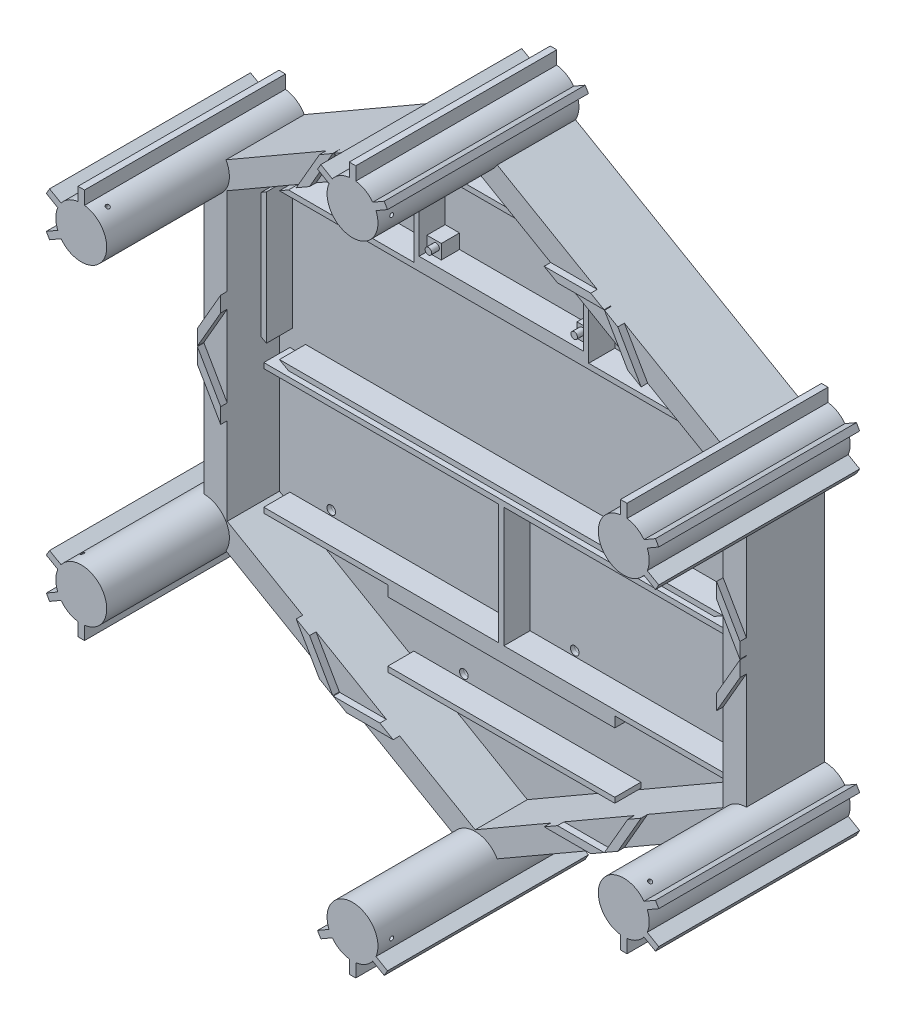
SolidWorks part; units mm, degrees
material "ABS"
ref_plane "Front Plane" through (0, 0, 0) normal (1, 0, 0) x (0, 1, 0)
ref_plane "Top Plane" through (0, 0, 0) normal (0, 0, 1) x (0, 1, 0)
ref_plane "Right Plane" through (0, 0, 0) normal (0, 1, 0) x (-1, 0, 0)
sketch "Sketch2" plane through (0, 0, 0) normal (0, 0, 1) x (0, 1, 0)
  line L0 (-1100, 0) -> (48900, 0) construction
  line L1 (120, 0) -> (60, 103.923)
  line L2 (60, 103.923) -> (-60, 103.923)
  line L3 (-60, 103.923) -> (-120, 0)
  line L4 (-120, 0) -> (-60, -103.923)
  line L5 (-60, -103.923) -> (60, -103.923)
  line L6 (60, -103.923) -> (120, 0)
  circle A0 centre (0, 0) radius 103.923 construction
  dimension "D1" = 120
extrude "Boss-Extrude1" add sketch "Sketch2" along normal mid plane 30
sketch "Sketch3" plane through (0, 0, 15) normal (0, 0, 1) x (1, 0, 0)
  line L0 (-95.0463, 65.125) -> (-76.4546, 75.8589) construction
  line L1 (-86.6025, 59.75) -> (-86.6025, 40.25) construction
  line L2 (-103.923, 60) -> (69.282, -40) construction
  line L3 (0, 0) -> (50000, 0) construction
  line L4 (0, 120) -> (-103.923, 60) construction
  line L5 (-111.6721, 54.0827) -> (-116.0719, 51.5425)
  line L6 (8.6603, 115) -> (43309.9304, -24885) construction
  line L7 (103.923, 50) -> (103.923, -49950) construction
  line L8 (95.2628, -65) -> (-43206.0074, -25065) construction
  line L9 (-8.6603, -115) -> (-43309.9304, 24885) construction
  line L10 (-86.6025, -50) -> (43214.6676, 24950) construction
  line L11 (0, -100) -> (0, 49900) construction
  line L14 (-117.3219, 66.2925) -> (-116.0719, 68.4575)
  line L16 (0, 0) -> (25000, 43301.2702) construction
  line L17 (0, 0) -> (25000, -43301.2702) construction
  line L18 (-114.0764, 61.9139) -> (-110.6886, 67.7817) construction
  line L19 (-112.9221, 63.7522) -> (-117.3219, 66.2925)
  line L20 (-111.6721, 65.9173) -> (-116.0719, 68.4575)
  line L21 (-112.9221, 56.2478) -> (-117.3219, 53.7075)
  line L23 (-105.173, 69.6695) -> (-105.173, 74.75)
  line L24 (-105.173, 74.75) -> (-102.673, 74.75)
  line L25 (-102.673, 69.6695) -> (-102.673, 74.75)
  line L26 (-117.3219, 53.7075) -> (-116.0719, 51.5425)
  line L27 (111.6721, -54.0827) -> (116.0719, -51.5425)
  line L28 (117.3219, -53.7075) -> (116.0719, -51.5425)
  line L29 (112.9221, -56.2478) -> (117.3219, -53.7075)
  line L30 (112.9221, -63.7522) -> (117.3219, -66.2925)
  line L31 (116.0719, -68.4575) -> (117.3219, -66.2925)
  line L32 (111.6721, -65.9173) -> (116.0719, -68.4575)
  line L33 (105.173, -69.6695) -> (105.173, -74.75)
  line L34 (105.173, -74.75) -> (102.673, -74.75)
  line L35 (102.673, -69.6695) -> (102.673, -74.75)
  line L36 (-8.9991, 123.7522) -> (-13.3989, 126.2925)
  line L37 (-12.1489, 128.4575) -> (-13.3989, 126.2925)
  line L38 (-7.7491, 125.9173) -> (-12.1489, 128.4575)
  line L39 (12.1489, 128.4575) -> (13.3989, 126.2925)
  line L40 (-1.25, 129.6695) -> (-1.25, 134.75)
  line L41 (1.25, 134.75) -> (-1.25, 134.75)
  line L42 (1.25, 129.6695) -> (1.25, 134.75)
  line L43 (7.7491, 125.9173) -> (12.1489, 128.4575)
  line L44 (8.9991, 123.7522) -> (13.3989, 126.2925)
  line L45 (-117.3219, -53.7075) -> (-116.0719, -51.5425)
  line L46 (-102.673, -69.6695) -> (-102.673, -74.75)
  line L47 (-105.173, -74.75) -> (-102.673, -74.75)
  line L48 (-105.173, -69.6695) -> (-105.173, -74.75)
  line L49 (-112.9221, -56.2478) -> (-117.3219, -53.7075)
  line L50 (-111.6721, -65.9173) -> (-116.0719, -68.4575)
  line L51 (-112.9221, -63.7522) -> (-117.3219, -66.2925)
  line L52 (-117.3219, -66.2925) -> (-116.0719, -68.4575)
  line L53 (-111.6721, -54.0827) -> (-116.0719, -51.5425)
  line L54 (102.673, 69.6695) -> (102.673, 74.75)
  line L55 (116.0719, 68.4575) -> (117.3219, 66.2925)
  line L56 (111.6721, 65.9173) -> (116.0719, 68.4575)
  line L57 (112.9221, 63.7522) -> (117.3219, 66.2925)
  line L58 (105.173, 69.6695) -> (105.173, 74.75)
  line L59 (112.9221, 56.2478) -> (117.3219, 53.7075)
  line L60 (117.3219, 53.7075) -> (116.0719, 51.5425)
  line L61 (111.6721, 54.0827) -> (116.0719, 51.5425)
  line L62 (105.173, 74.75) -> (102.673, 74.75)
  line L63 (8.9991, -123.7522) -> (13.3989, -126.2925)
  line L64 (7.7491, -125.9173) -> (12.1489, -128.4575)
  line L65 (1.25, -129.6695) -> (1.25, -134.75)
  line L66 (1.25, -134.75) -> (-1.25, -134.75)
  line L67 (-1.25, -129.6695) -> (-1.25, -134.75)
  line L68 (12.1489, -128.4575) -> (13.3989, -126.2925)
  line L69 (-7.7491, -125.9173) -> (-12.1489, -128.4575)
  line L70 (-12.1489, -128.4575) -> (-13.3989, -126.2925)
  line L71 (-8.9991, -123.7522) -> (-13.3989, -126.2925)
  arc A0 (-1.25, 129.6695) -> (-7.7491, 125.9173) centre (0, 120) ccw
  arc A1 (112.9221, 56.2478) -> (112.9221, 63.7522) centre (103.923, 60) ccw
  arc A2 (105.173, -69.6695) -> (111.6721, -65.9173) centre (103.923, -60) ccw
  arc A3 (-7.7491, -125.9173) -> (-1.25, -129.6695) centre (0, -120) ccw
  arc A4 (-112.9221, -56.2478) -> (-112.9221, -63.7522) centre (-103.923, -60) ccw
  arc A5 (-112.9221, 63.7522) -> (-112.9221, 56.2478) centre (-103.923, 60) ccw
  arc A6 (-105.173, 69.6695) -> (-111.6721, 65.9173) centre (-103.923, 60) ccw
  arc A7 (-111.6721, 54.0827) -> (-102.673, 69.6695) centre (-103.923, 60) ccw
  arc A8 (-111.6721, -65.9173) -> (-105.173, -69.6695) centre (-103.923, -60) ccw
  arc A9 (-102.673, -69.6695) -> (-111.6721, -54.0827) centre (-103.923, -60) ccw
  arc A10 (1.25, -129.6695) -> (7.7491, -125.9173) centre (0, -120) ccw
  arc A11 (8.9991, -123.7522) -> (-8.9991, -123.7522) centre (0, -120) ccw
  arc A12 (112.9221, -63.7522) -> (112.9221, -56.2478) centre (103.923, -60) ccw
  arc A13 (111.6721, -54.0827) -> (102.673, -69.6695) centre (103.923, -60) ccw
  arc A14 (111.6721, 65.9173) -> (105.173, 69.6695) centre (103.923, 60) ccw
  arc A15 (102.673, 69.6695) -> (111.6721, 54.0827) centre (103.923, 60) ccw
  arc A16 (7.7491, 125.9173) -> (1.25, 129.6695) centre (0, 120) ccw
  arc A17 (-8.9991, 123.7522) -> (8.9991, 123.7522) centre (0, 120) ccw
  dimension "D1" = 19.5
  dimension "D2" = 5
  dimension "D3" = 1.25
  dimension "D4" = 1.25
  dimension "D5" = 14.75
  dimension "D6" = 2.5
extrude "Boss-Extrude2" add sketch "Sketch3" against normal up to surface (30 mm away) and the other way blind 47 up to face at (0, 0, -15)
sketch "Sketch4" plane through (0, 0, 15) normal (0, 0, 1) x (1, 0, 0)
  line L0 (0, -1000) -> (0, 49000) construction
  line L2 (0, 109.6966) -> (-95, 54.8483)
  line L3 (-95, 54.8483) -> (-95, -54.8483)
  line L4 (-95, -54.8483) -> (0, -109.6966)
  line L5 (0, -109.6966) -> (95, -54.8483)
  line L6 (95, -54.8483) -> (95, 54.8483)
  line L7 (95, 54.8483) -> (0, 109.6966)
  circle A0 centre (0, 0) radius 95 construction
  dimension "D1" = 95
extrude "Cut-Extrude1" cut sketch "Sketch4" against normal blind 20
sketch "Sketch5" plane through (0, 0, -5) normal (0, 0, 1) x (1, 0, 0)
  line L0 (-1, -53.1517) -> (-91, -53.1517)
  line L1 (-95, 54.8483) -> (-95, -54.8483) construction
  line L3 (-90, 1.735) -> (-90, 51.9615)
  line L5 (90, 1.735) -> (90, 51.9615)
  line L6 (33.5, 56.8483) -> (33.5, 92.8483)
  line L7 (-1000, 0) -> (49000, 0) construction
  line L8 (0, -1000) -> (0, 49000) construction
  line L9 (-6, -53.1517) -> (-6, -7.1517) construction
  line L10 (91, -53.1517) -> (1, -53.1517)
  line L11 (89, -53.1517) -> (89, -7.1517) construction
  line L12 (91, -7.1517) -> (1, -7.1517)
  line L13 (6, -53.1517) -> (6, -7.1517) construction
  line L14 (33.5, 92.8483) -> (-33.5, 92.8483)
  line L15 (-33.5, 56.8483) -> (-33.5, 92.8483)
  line L16 (-1, -7.1517) -> (-91, -7.1517)
  line L17 (-89, -53.1517) -> (-89, -7.1517) construction
  line L19 (43.5, -82.1517) -> (-43.5, -82.1517)
  line L20 (41.5, -82.1517) -> (41.5, -59.1517) construction
  line L21 (43.5, -59.1517) -> (-43.5, -59.1517)
  line L22 (-41.5, -82.1517) -> (-41.5, -59.1517) construction
  line L23 (-92, 2.8897) -> (-92, 50.8068)
  line L24 (-81.5359, 56.8483) -> (-33.5, 56.8483)
  line L25 (31.5, 59.8483) -> (-31.5, 59.8483)
  line L26 (31.5, 59.8483) -> (31.5, 90.8483)
  line L27 (31.5, 90.8483) -> (-31.5, 90.8483)
  line L28 (-31.5, 59.8483) -> (-31.5, 90.8483)
  line L29 (0, 90.8483) -> (0, 59.8483) construction
  line L30 (31.5, 75.3483) -> (-31.5, 75.3483) construction
  line L31 (92, 2.8897) -> (92, 50.8068)
  line L34 (-91, -55.1517) -> (-91, -5.1517) construction
  line L36 (-4, -55.1517) -> (-4, -5.1517) construction
  line L37 (91, -55.1517) -> (91, -5.1517) construction
  line L39 (4, -55.1517) -> (4, -5.1517) construction
  line L40 (91, -55.1517) -> (43.5, -55.1517)
  line L41 (43.5, -84.1517) -> (43.5, -57.1517) construction
  line L43 (-43.5, -84.1517) -> (-43.5, -57.1517) construction
  line L44 (43.5, -84.1517) -> (-43.5, -84.1517)
  line L45 (-6, -7.1517) -> (-89, -7.1517) construction
  line L46 (-6, -53.1517) -> (-89, -53.1517) construction
  line L47 (-91, -5.1517) -> (-91, -7.1517)
  line L50 (-91, -53.1517) -> (-91, -55.1517)
  line L51 (89, -7.1517) -> (6, -7.1517) construction
  line L52 (89, -53.1517) -> (6, -53.1517) construction
  line L54 (91, -5.1517) -> (91, -7.1517)
  line L55 (91, -53.1517) -> (91, -55.1517)
  line L60 (43.5, -57.1517) -> (-43.5, -57.1517) construction
  line L62 (-92, -3.1517) -> (92, -3.1517) construction
  line L63 (41.5, -82.1517) -> (-41.5, -82.1517) construction
  line L64 (41.5, -59.1517) -> (-41.5, -59.1517) construction
  line L65 (-43.5, -55.1517) -> (-43.5, -59.1517)
  line L66 (-43.5, -82.1517) -> (-43.5, -84.1517)
  line L67 (43.5, -84.1517) -> (43.5, -82.1517)
  line L68 (43.5, -82.1517) -> (43.5, -59.1517)
  line L69 (43.5, -55.1517) -> (43.5, -59.1517)
  line L70 (91, -5.1517) -> (4, -5.1517) construction
  line L71 (-4, -5.1517) -> (-91, -5.1517) construction
  line L72 (-1, -7.1517) -> (-1, -53.1517)
  line L73 (1, -7.1517) -> (1, -53.1517)
  line L74 (-4, -55.1517) -> (-91, -55.1517) construction
  line L75 (91, -55.1517) -> (4, -55.1517) construction
  line L76 (-43.5, -55.1517) -> (-91, -55.1517)
  line L77 (33.5, 57.8483) -> (-33.5, 57.8483) construction
  line L78 (-33.5, 57.8483) -> (-33.5, 92.8483) construction
  line L79 (33.5, 57.8483) -> (33.5, 92.8483) construction
  line L80 (33.5, 56.8483) -> (81.5359, 56.8483)
  line L81 (-92, 56.8483) -> (92, 56.8483) construction
  line L82 (-29.2, 90.8483) -> (-29.2, 59.8483) construction
  line L83 (29.2, 90.8483) -> (29.2, 59.8483) construction
  line L84 (-31.5, 88.1483) -> (31.5, 88.1483) construction
  line L85 (-31.5, 62.0483) -> (31.5, 62.0483) construction
  line L86 (-92, 50.8068) -> (-90, 51.9615)
  line L87 (0, 109.6966) -> (-95, 54.8483) construction
  line L88 (0, 109.6966) -> (-95, 54.8483) construction
  line L89 (-85, 54.8483) -> (-81.5359, 56.8483)
  line L90 (-90, -1.1517) -> (-90, 54.8483) construction
  line L91 (-92, -3.1517) -> (-92, 56.8483) construction
  line L92 (-90, 54.8483) -> (90, 54.8483) construction
  line L93 (-85, 54.8483) -> (85, 54.8483)
  line L94 (-92, 50.8068) -> (-81.5359, 56.8483) construction
  line L95 (92, 50.8068) -> (81.5359, 56.8483) construction
  line L96 (81.5359, 56.8483) -> (85, 54.8483)
  line L97 (90, -1.1517) -> (90, 54.8483) construction
  line L98 (90, 51.9615) -> (92, 50.8068)
  line L99 (92, -3.1517) -> (92, 56.8483) construction
  line L100 (-81.5359, -3.1517) -> (81.5359, -3.1517)
  line L101 (-91, -5.1517) -> (91, -5.1517)
  line L102 (-1045.1246, 26.8483) -> (48954.8754, 26.8483) construction
  line L103 (90, 1.735) -> (92, 2.8897)
  line L104 (81.5359, -3.1517) -> (85, -1.1517)
  line L105 (92, 2.8897) -> (81.5359, -3.1517) construction
  line L106 (-85, -1.1517) -> (-81.5359, -3.1517)
  line L107 (-92, 2.8897) -> (-90, 1.735)
  line L108 (-92, 2.8897) -> (-81.5359, -3.1517) construction
  line L109 (-90, -1.1517) -> (90, -1.1517) construction
  line L110 (-85, -1.1517) -> (85, -1.1517)
  circle A0 centre (-27.95, 86.8983) radius 1.25
  circle A1 centre (27.95, 86.8983) radius 1.25
  circle A2 centre (27.95, 63.2983) radius 1.25
  circle A3 centre (-27.95, 63.2983) radius 1.25
  point P13 (0, 75.3483)
  point P61 (0, -82.1517)
  dimension "D28" = 2.5
  dimension "D2" = 83
  dimension "D3" = 46
  dimension "D4" = 23
  dimension "D5" = 83
  dimension "D6" = 31
  dimension "D7" = 63
  dimension "D8" = 12
  dimension "D9" = 6
  dimension "D10" = 6
  dimension "D11" = 6
  dimension "D12" = 46
  dimension "D13" = 182
  dimension "D14" = 6
  dimension "D15" = 16.8483
  dimension "D17" = 180
  dimension "D22" = 1
  dimension "D23" = 1
  dimension "D24" = 2.7
  dimension "D25" = 2.2
  dimension "D26" = 2.3
  dimension "D27" = 2.3
  dimension "D29" = 5
  dimension "D30" = 5
  dimension "D31" = 2
  dimension "D32" = 28
  dimension "D18" = 2
  dimension "D19" = 2
  dimension "D20" = 2
  dimension "D21" = 2
extrude "Boss-Extrude3" add sketch "Sketch5" along normal blind 10 contours L5 L103 L31 L98 | L110 L106 L100 L104 | L23 L107 L3 L86 | L3 L86 L23 L100 L31 L98 L5 L110 | A0 | A1 | A3 | A2 | L6 L14 L15 L24 L89 L93 L96 L80 | L21 L65 L76 L50 L0 L72 L16 L47 L101 L54 L12 L73 L10 L55 L40 L69 | L26 L25 L28 L27 | L67 L19 L66 L44 region at (-90.9922, 26.8483, -5) region at (90.9922, 26.8483, -5) region at (0, -2.1448, -5)
sketch "Sketch7" plane through (0, 0, -5) normal (0, 0, 1) x (1, 0, 0)
  line L0 (-1031.5, 75.3483) -> (48968.5, 75.3483) construction
  line L1 (31.5, 90.8483) -> (-31.5, 90.8483) construction
  line L2 (0, -1000) -> (0, 49000) construction
  line L3 (31.5, 85.3483) -> (26, 85.3483)
  line L4 (-31.5, 90.8483) -> (-26, 90.8483)
  line L5 (-31.5, 90.8483) -> (-31.5, 85.3483)
  line L6 (-31.5, 85.3483) -> (-26, 85.3483)
  line L7 (-26, 90.8483) -> (-26, 85.3483)
  line L8 (26, 90.8483) -> (26, 85.3483)
  line L9 (31.5, 90.8483) -> (26, 90.8483)
  line L10 (31.5, 90.8483) -> (31.5, 85.3483)
  line L11 (-31.5, 65.3483) -> (-26, 65.3483)
  line L12 (-26, 59.8483) -> (-26, 65.3483)
  line L13 (-31.5, 59.8483) -> (-26, 59.8483)
  line L14 (-31.5, 59.8483) -> (-31.5, 65.3483)
  line L15 (31.5, 59.8483) -> (31.5, 65.3483)
  line L16 (31.5, 59.8483) -> (26, 59.8483)
  line L17 (26, 59.8483) -> (26, 65.3483)
  line L18 (31.5, 65.3483) -> (26, 65.3483)
  line L19 (-31.5, 59.8483) -> (-31.5, 90.8483) construction
  line L22 (31.5, 59.8483) -> (-31.5, 59.8483) construction
  line L23 (31.5, 90.8483) -> (-31.5, 90.8483) construction
  point P26 (23968.5, 75.3483)
  point P27 (23968.5, 75.3483)
  dimension "D1" = 5.5
  dimension "D2" = 15.5
extrude "Boss-Extrude4" add sketch "Sketch7" along normal blind 7
sketch "Sketch8" plane through (0, 0, -5) normal (0, 0, 1) x (1, 0, 0)
  line L0 (-6, -1025.7577) -> (-6, 48974.2423) construction
  line L1 (6, -1023.6348) -> (6, 48976.3652) construction
  line L2 (-89, -1019.8608) -> (-89, 48980.1392) construction
  line L3 (89, -1021.6) -> (89, 48978.4) construction
  line L4 (-1, -7.1517) -> (-1, -53.1517) construction
  line L5 (1, -7.1517) -> (1, -53.1517) construction
  line L6 (-73.5, -7.1517) -> (-73.5, -53.1517) construction
  line L7 (-1, -7.1517) -> (-91, -7.1517) construction
  line L8 (-1, -53.1517) -> (-91, -53.1517) construction
  line L9 (-21.5, -7.1517) -> (-21.5, -53.1517) construction
  line L11 (16.5, -7.1517) -> (16.5, -53.1517) construction
  line L14 (73.5, -53.1517) -> (73.5, -7.1517) construction
  line L15 (91, -53.1517) -> (1, -53.1517) construction
  line L16 (91, -7.1517) -> (1, -7.1517) construction
  line L19 (-41.5, -59.1517) -> (-41.5, -82.1517) construction
  line L21 (43.5, -59.1517) -> (-43.5, -59.1517) construction
  line L22 (43.5, -82.1517) -> (-43.5, -82.1517) construction
  line L23 (41.5, -82.1517) -> (41.5, -59.1517) construction
  line L26 (43.5, -55.1517) -> (43.5, -59.1517) construction
  line L27 (43.5, -82.1517) -> (-43.5, -82.1517) construction
  line L28 (26, -82.1517) -> (26, -59.1517) construction
  line L29 (-26, -59.1517) -> (-26, -82.1517) construction
  line L30 (91, -53.1517) -> (1, -53.1517) construction
  line L31 (43.5, -59.1517) -> (-43.5, -59.1517) construction
  line L32 (-43.5, -55.1517) -> (-43.5, -59.1517) construction
  circle A1 centre (-75.15, -51.1517) radius 1.65
  circle A2 centre (-19.85, -9.1517) radius 1.65
  circle A3 centre (18.15, -51.1517) radius 1.65
  circle A4 centre (71.85, -9.1517) radius 1.65
  circle A5 centre (-24.35, -80.1517) radius 1.65
  circle A7 centre (24.35, -61.1517) radius 1.65
  dimension "D6" = 3.3
  dimension "D14" = 2
  dimension "D19" = 2
  dimension "D1" = 5
  dimension "D2" = 5
  dimension "D3" = 83
  dimension "D4" = 15.5
  dimension "D5" = 15.5
  dimension "D7" = 2
  dimension "D8" = 2
  dimension "D9" = 83
  dimension "D10" = 15.5
  dimension "D11" = 15.5
  dimension "D12" = 2
  dimension "D13" = 2
  dimension "D15" = 2
  dimension "D16" = 2
  dimension "D17" = 15.5
  dimension "D18" = 15.5
extrude "Cut-Extrude2" cut sketch "Sketch8" against normal blind 1.5
sketch "Sketch9" plane through (0, 0, -6.5) normal (0, 0, 1) x (1, 0, 0)
  circle A0 centre (-75.15, -51.1517) radius 1.8
  circle A1 centre (-19.85, -9.1517) radius 1.8
  circle A2 centre (18.15, -51.1517) radius 1.8
  circle A3 centre (24.35, -61.1517) radius 1.8
  circle A4 centre (-24.35, -80.1517) radius 1.8
  circle A5 centre (71.85, -9.1517) radius 1.8
  dimension "D1" = 3.6
extrude "Cut-Extrude3" cut sketch "Sketch9" against normal blind 2.5
sketch "Sketch10" plane through (0, 0, 15) normal (0, 0, 1) x (1, 0, 0)
  line L0 (-1000, 0) -> (49000, 0) construction
  line L1 (0, -1000) -> (0, 49000) construction
  line L2 (-8.4437, 115.125) -> (-95.4793, 64.875) construction
  line L3 (-103.923, 0) -> (-51.9615, -90) construction
  line L4 (-51.9615, -90) -> (51.9615, -90) construction
  line L5 (51.9615, -90) -> (103.923, 0) construction
  line L6 (103.923, 0) -> (51.9615, 90) construction
  line L7 (51.9615, 90) -> (-51.9615, 90) construction
  line L8 (-51.9615, 90) -> (-103.923, 0) construction
  line L10 (60.9712, -74.4948) -> (52.0481, -89.95)
  line L11 (57.1577, -87) -> (52.0481, -89.95)
  line L12 (-66.0807, -71.5448) -> (-57.1577, -87)
  line L13 (-95, -54.8483) -> (0, -109.6966) construction
  line L14 (-95.4793, -64.875) -> (-8.4437, -115.125) construction
  line L15 (-46.7654, -93) -> (-28.9193, -93)
  line L17 (-95, -54.8483) -> (0, -109.6966) construction
  line L19 (66.0807, -71.5448) -> (57.1577, -87)
  line L20 (95, -15.5552) -> (95, -21.4552)
  line L21 (95, -21.4552) -> (103.923, -6)
  line L28 (103.923, -6) -> (103.923, -0.1)
  line L70 (-95, -15.5552) -> (-103.923, -0.1)
  line L71 (-60.9712, -74.4948) -> (-52.0481, -89.95)
  line L72 (-59.4531, -77.1242) -> (-54.9981, -84.8405) construction
  line L73 (-45.9749, -90.05) -> (-37.065, -90.05) construction
  line L74 (-51.8749, -90.05) -> (-34.0288, -90.05)
  line L75 (-103.923, -6) -> (-103.923, -0.1)
  line L76 (-54.9981, -84.8405) -> (-50.4865, -87.4452) construction
  line L77 (-45.9749, -90.05) -> (-50.4865, -87.4452) construction
  line L78 (-57.1577, -87) -> (-51.9615, -90) construction
  line L79 (-46.7654, -93) -> (-51.9615, -90) construction
  line L80 (-57.1577, -87) -> (-52.0481, -89.95)
  line L81 (-51.8749, -90.05) -> (-46.7654, -93)
  line L82 (-34.1154, -90) -> (-28.9193, -93) construction
  line L83 (-60.9712, -74.4948) -> (-66.0807, -71.5448)
  line L84 (-34.0288, -90.05) -> (-28.9193, -93)
  line L85 (-66.0807, -71.5448) -> (-60.8846, -74.5448) construction
  line L86 (60.9712, -74.4948) -> (66.0807, -71.5448)
  line L87 (51.8749, -90.05) -> (34.0288, -90.05)
  line L88 (51.8749, -90.05) -> (46.7654, -93)
  line L89 (46.7654, -93) -> (28.9193, -93)
  line L90 (34.0288, -90.05) -> (28.9193, -93)
  line L91 (-95, 54.8483) -> (43206.2702, -24945.1517) construction
  line L92 (95, -15.5552) -> (103.923, -0.1)
  line L93 (103.923, 0.1) -> (103.923, 6)
  line L94 (103.923, 6) -> (95, 21.4552)
  line L95 (95, 15.5552) -> (95, 21.4552)
  line L96 (103.923, 0.1) -> (95, 15.5552)
  line L97 (34.0288, 90.05) -> (51.8749, 90.05)
  line L98 (46.7654, 93) -> (51.8749, 90.05)
  line L99 (28.9193, 93) -> (46.7654, 93)
  line L100 (34.0288, 90.05) -> (28.9193, 93)
  line L101 (52.0481, 89.95) -> (60.9712, 74.4948)
  line L102 (52.0481, 89.95) -> (57.1577, 87)
  line L103 (57.1577, 87) -> (66.0807, 71.5448)
  line L104 (60.9712, 74.4948) -> (66.0807, 71.5448)
  line L106 (-37.065, -90.05) -> (-37.065, -90.05) construction
  line L107 (-59.4531, -77.1242) -> (-59.4531, -77.1242) construction
  line L108 (-95, -21.4552) -> (-103.923, -6)
  line L109 (-95, -15.5552) -> (-95, -21.4552)
  line L110 (-103.923, 0.1) -> (-95, 15.5552)
  line L111 (-95, 15.5552) -> (-95, 21.4552)
  line L112 (-103.923, 6) -> (-95, 21.4552)
  line L113 (-103.923, 0.1) -> (-103.923, 6)
  line L114 (-52.0481, 89.95) -> (-57.1577, 87)
  line L115 (-57.1577, 87) -> (-66.0807, 71.5448)
  line L116 (-60.9712, 74.4948) -> (-66.0807, 71.5448)
  line L117 (-52.0481, 89.95) -> (-60.9712, 74.4948)
  line L118 (-34.0288, 90.05) -> (-28.9193, 93)
  line L119 (-28.9193, 93) -> (-46.7654, 93)
  line L120 (-46.7654, 93) -> (-51.8749, 90.05)
  line L121 (-34.0288, 90.05) -> (-51.8749, 90.05)
  circle A0 centre (0, 0) radius 90 construction
  dimension "D1" = 0.1
  dimension "D2" = 2.95
  dimension "D3" = 0.1732
extrude "Boss-Extrude9" add sketch "Sketch10" along normal blind 2.5 contours L10 L11 L19 L86 | L83 L12 L80 L71 | L84 L15 L81 L74 | L87 L90 L89 L88 | L20 L21 L28 L92 | L93 L94 L95 L96 | L101 L104 L103 L102 | L97 L98 L99 L100 | L118 L119 L120 L121 | L114 L115 L116 L117 | L110 L111 L112 L113 | L70 L75 L108 L109
sketch "Sketch13" plane through (103.923, 0, 0) normal (1, 0, 0) x (0, 1, 0)
  line L0 (-1114.0093, 56) -> (48885.9907, 56) construction
  line L1 (-110.25, 62) -> (-123.7522, 62) construction
  line L2 (-1104.4267, 56.75) -> (48895.5733, 56.75) construction
  line L3 (-120, -948.4524) -> (-120, 49051.5476) construction
  line L6 (-110.25, 15) -> (-110.25, 62) construction
  line L7 (0, -1000) -> (0, 49000) construction
  circle A0 centre (-120, 56.75) radius 0.75
  circle A1 centre (120, 56.75) radius 0.75
  dimension "D4" = 1.5
  dimension "D1" = 6
  dimension "D3" = 9.75
extrude "Cut-Extrude5" cut sketch "Sketch13" against normal through all
sketch "Sketch14" plane through (51.9615, -90, 0) normal (0.5, -0.866, 0) x (0.866, 0.5, 0)
  line L0 (-1119.1763, 56) -> (48880.8237, 56) construction
  line L1 (-1109.5937, 56.75) -> (48890.4063, 56.75) construction
  line L2 (-120, -948.4524) -> (-120, 49051.5476) construction
  line L3 (0, -1028.0633) -> (0, 48971.9367) construction
  line L4 (-110.25, 62) -> (-123.7522, 62) construction
  line L5 (-110.25, 15) -> (-110.25, 62) construction
  circle A0 centre (-120, 56.75) radius 0.75
  circle A1 centre (120, 56.75) radius 0.75
  dimension "D1" = 1.5
  dimension "D2" = 6
  dimension "D4" = 9.75
extrude "Cut-Extrude6" cut sketch "Sketch14" against normal through all
sketch "Sketch15" plane through (-51.9615, -90, 0) normal (-0.5, -0.866, 0) x (0.866, -0.5, 0)
  line L0 (-1110.1642, 56) -> (48889.8358, 56) construction
  line L1 (-1104.4267, 56.75) -> (48895.5733, 56.75) construction
  line L2 (-120, -979.709) -> (-120, 49020.291) construction
  line L3 (0, -1031.2566) -> (0, 48968.7434) construction
  line L4 (-110.25, 15) -> (-110.25, 62) construction
  line L5 (-110.25, 62) -> (-123.7522, 62) construction
  circle A0 centre (-120, 56.75) radius 0.75
  circle A1 centre (120, 56.75) radius 0.75
  dimension "D1" = 1.5
  dimension "D2" = 9.75
  dimension "D4" = 6
extrude "Cut-Extrude7" cut sketch "Sketch15" against normal through all
